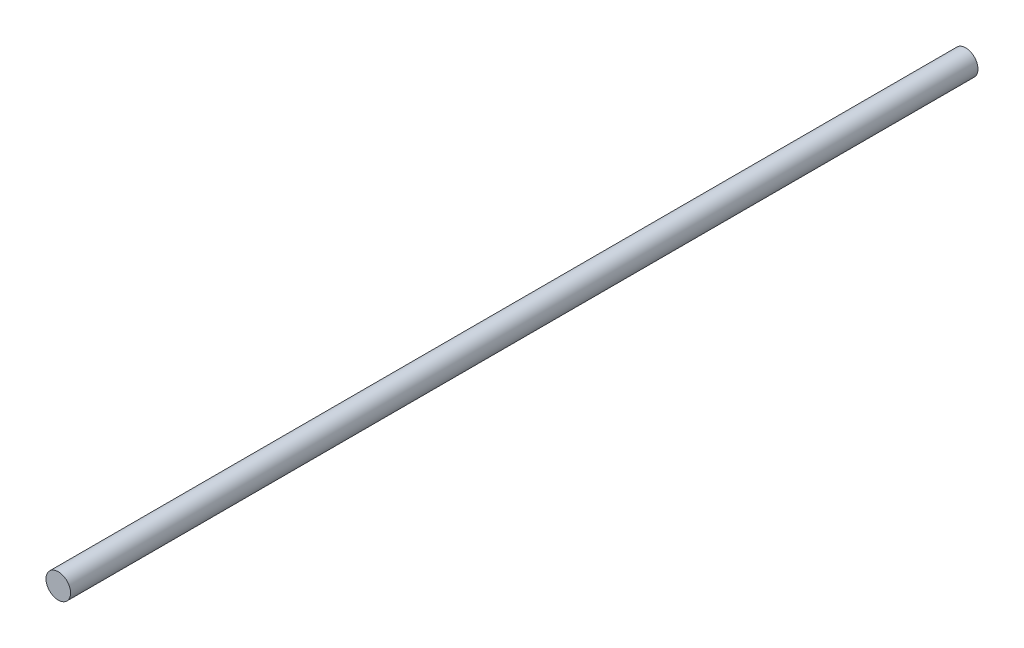
SolidWorks part; units mm, degrees
material "AISI 316 Stainless Steel Sheet (SS)"
ref_plane "Front (1)" through (0, 0, 0) normal (0, 0, 1) x (1, 0, 0)
ref_plane "Top (2)" through (0, 0, 0) normal (0, 1, 0) x (1, 0, 0)
ref_plane "Right (3)" through (0, 0, 0) normal (1, 0, 0) x (0, 0, -1)
ref_axis "X Axis" through (13.5064, 0, 0) along (-1, 0, 0)
ref_axis "Y Axis" through (0, 12.3593, 0) along (0, -1, 0)
ref_axis "Z Axis" through (0, 0, 14.1119) along (0, 0, -1)
sketch "Sketch2" plane through (0, 0, 0) normal (1, 0, 0) x (0, 0, -1)
  line L1 (0, 0) -> (295, 0)
  line L2 (0, 0) -> (0, 4)
  line L3 (0, 4) -> (295, 4)
  line L4 (295, 0) -> (295, 4)
  dimension "D1" = 295
  dimension "D2" = 4
revolve "Revolve1" add sketch "Sketch2" angle 360 about L1
cosmetic thread "Cosmetic Thread2" parameters "D2"=6.891
